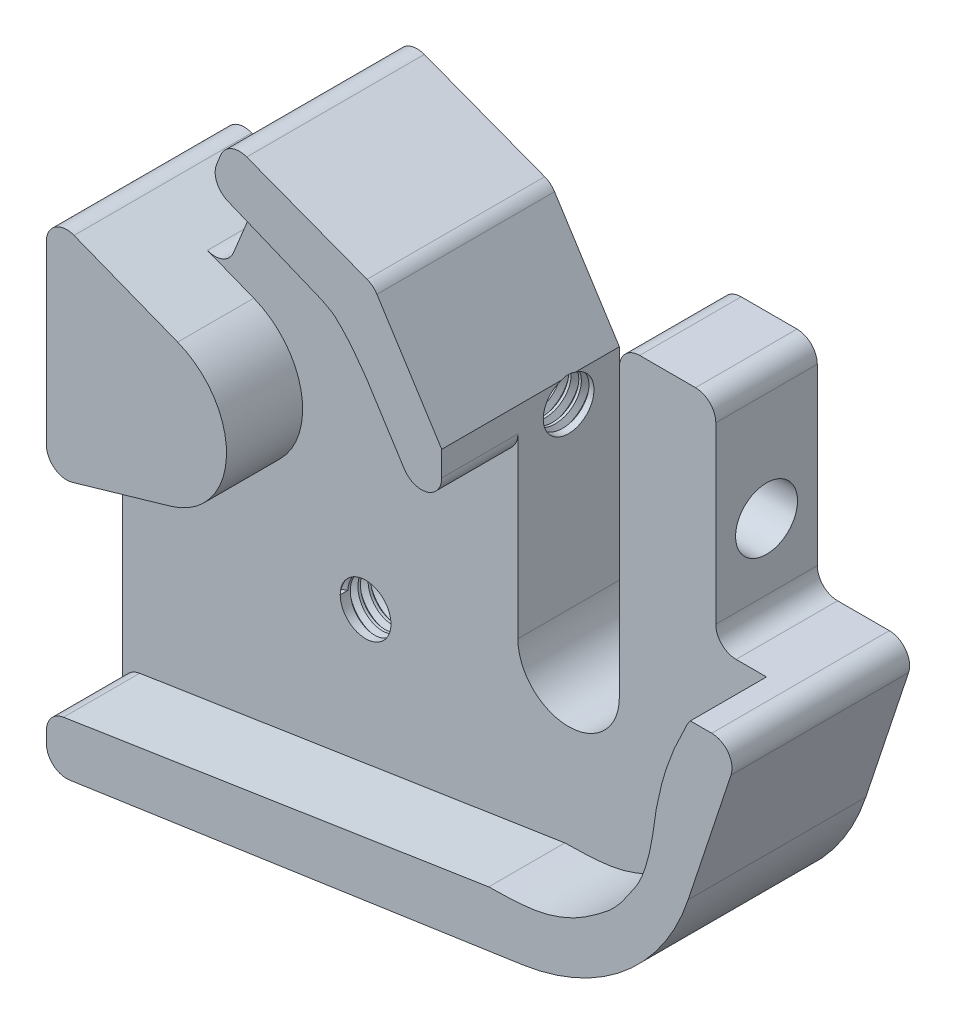
SolidWorks part; units mm, degrees
ref_plane "Front Plane" through (0, 0, 0) normal (0, 0, 1) x (1, 0, 0)
ref_plane "Top Plane" through (0, 0, 0) normal (0, 1, 0) x (1, 0, 0)
ref_plane "Right Plane" through (0, 0, 0) normal (1, 0, 0) x (0, 0, -1)
sketch "Sketch1" plane through (0, 0, 0) normal (0, 0, 1) x (1, 0, 0)
  line L0 (169.0465, 531.5792) -> (1384.9618, 942.3347) construction
  line L1 (17.1755, 0.269) -> (145.8355, -18.3486) construction
  line L2 (78.9683, 43.5936) -> (88.9683, 43.5936)
  line L3 (88.9683, 43.5936) -> (88.9683, 26.5936)
  line L4 (88.9683, 26.5936) -> (78.9683, 26.5936)
  line L5 (78.9683, 26.5936) -> (78.9683, 43.5936)
  line L6 (77.9414, 43.8024) -> (71.5407, 53.8656)
  line L7 (56.0381, 62.9033) -> (67.1668, 58.333)
  line L8 (88.9683, 43.5936) -> (88.9683, 61.7655)
  line L9 (88.9683, 61.7655) -> (98.4683, 61.7655)
  line L10 (77.9414, 43.8024) -> (78.9683, 42.1878)
  line L11 (20.6229, 24.1202) -> (53.1029, 33.5417)
  line L12 (23.9133, 59.0209) -> (55.1963, 46.7648)
  line L13 (56.0381, 62.9033) -> (50.2123, 48.7174)
  line L14 (70.5008, 62.7543) -> (72.231, 62.0968)
  line L15 (20.6228, 1.7639) -> (20.6229, 24.1202)
  line L16 (20.6229, 24.1202) -> (20.6229, 30.1202)
  line L17 (103.2745, 61.7655) -> (98.4683, 61.7655)
  line L18 (20.6229, 30.1202) -> (43.6301, 36.7939)
  line L19 (23.9133, 59.0209) -> (22.0894, 54.3655)
  line L20 (22.0894, 54.3655) -> (44.4958, 45.587)
  line L21 (78.9683, 43.5936) -> (78.9683, 49.4415)
  line L22 (57.9376, 67.5285) -> (70.5008, 62.7543)
  line L24 (40.0198, 35.7467) -> (40.0198, 47.3406)
  line L25 (40.0198, 47.3406) -> (40.0198, 52.7107)
  line L26 (56.0381, 62.9033) -> (57.9376, 67.5285)
  line L27 (103.4635, 40.5809) -> (108.336, 40.5809)
  line L28 (40.0198, 35.7467) -> (40.0198, 4.6135)
  line L29 (108.336, 40.5809) -> (99.307, 13.3233)
  line L30 (98.4683, 61.7655) -> (98.4683, 40.5809)
  line L31 (99.307, 13.3233) -> (20.6228, 1.7639)
  line L32 (83.9683, 43.5936) -> (83.9683, 46.6936)
  line L33 (20.6228, 6.4639) -> (20.6228, 6.7639)
  line L34 (20.6228, 6.7639) -> (83.6, 16.4882)
  line L35 (20.6229, 30.1202) -> (20.6229, 61.7655)
  line L36 (23.9133, 59.0209) -> (20.6229, 60.3101)
  line L37 (22.0894, 54.3655) -> (20.6229, 54.94)
  line L38 (73.7743, 50.3539) -> (77.9932, 53.0374) construction
  line L39 (77.9932, 53.0374) -> (71.1704, 63.7644)
  line L40 (77.9932, 53.0374) -> (78.9683, 51.5043)
  line L41 (78.9683, 51.5043) -> (78.9683, 49.4415)
  line L47 (98.4683, 40.5809) -> (103.4635, 40.5809)
  circle A0 centre (83.9683, 31.5936) radius 5
  circle A1 centre (83.9683, 38.5936) radius 5
  circle A5 centre (50.1903, 40.5872) radius 7.578
  circle A6 centre (103.2745, 54.3655) radius 4.4
  circle A7 centre (103.2745, 54.3655) radius 7.4
  circle A8 centre (83.9683, 31.5936) radius 20.3057
  spline S0 degree 3 poles (67.1668, 58.333) (67.5307, 58.1482) (68.2163, 57.8297) (69.7375, 56.3376) (70.7671, 54.998) (71.5407, 53.8656) knots 0 0 0 0 0.194176 0.353383 1 1 1 1
  spline S1 degree 3 poles (83.6, 16.4882) (85.4172, 16.5376) (87.878, 16.5192) (90.6726, 17.4205) (92.3949, 18.1773) (94.0998, 19.3373) (95.7619, 20.5842) (96.8381, 21.8934) (97.5722, 23.0215) (98.2993, 24.0127) (98.8168, 25.1807) (99.3382, 26.7948) (99.7545, 28.7331) (99.9792, 30.8782) (100.4112, 32.873) (100.8434, 34.6928) (101.4168, 36.2088) (101.8572, 37.4461) (102.3579, 38.4137) (102.8415, 39.4999) (103.165, 40.2018) (103.4635, 40.5809) knots 0 0 0 0 0.157684 0.206761 0.251698 0.319001 0.383658 0.429514 0.463788 0.499543 0.534878 0.573031 0.645405 0.704849 0.75836 0.820852 0.865423 0.897677 0.933689 0.958942 1 1 1 1
  spline S2 degree 3 poles (103.4635, 40.5809) (103.5281, 40.7021) (103.6539, 40.9177) (103.7777, 41.1891) (104.0324, 41.5752) (104.2845, 42.0418) (104.6133, 42.6639) (105.0506, 43.3284) (105.5376, 44.1633) (106.1189, 44.9679) (106.7473, 45.8247) (107.3304, 46.576) (107.8594, 47.2965) (108.3783, 47.8664) (108.8492, 48.4246) (109.2415, 48.9281) (109.5877, 49.4941) (110.1609, 50.7988) (110.3782, 52.0409) (110.5419, 52.9707) knots 0 0 0 0 0.032133 0.040138 0.080049 0.114202 0.15475 0.224504 0.279876 0.355143 0.430433 0.500504 0.552615 0.615873 0.660356 0.704255 0.748281 0.797656 1 1 1 1
  dimension "D7" = 5
  dimension "D5" = 8.8
  dimension "D6" = 14.8
  dimension "D1" = 130
  dimension "D2" = 10
  dimension "D3" = 17
  dimension "D4" = 9.5
  dimension "D8" = 5
  dimension "D9" = 5
  dimension "D10" = 5
extrude "Boss-Extrude1" add sketch "Sketch1" along normal blind 10 contours L34 S1 A8 L47 L30 L8 L3 L4 L5 L10 L6 | S0 L7 L13 L12 A5 L11 L28 L34 A8 L6 | A0 L5 L4 | A0 L4 L3 | A8 L30 A7 L9 L8 | A8 S1 L47 | L30 A7 region at (78.4335, 40.3907, 0) region at (93.3717, 55.5464, 0) region at (87.8514, 27.7104, 0) region at (80.0851, 27.7104, 0) region at (56.6282, 32.8832, 0) region at (97.4134, 54.3655, 0) region at (102.785, 40.1666, 0)
extrude "Boss-Extrude2" add sketch "Sketch1<3>" along normal blind 17.5 contours L7 S0 L6 A8 L41 L40 L39 L14 L22 L26 | L41 A8 L6 L10 L5 L21 | A5 | A5 L12 L25 L20 | A5 L20 L24 L18 | A5 L18 L28 L11 | A8 L34 L28 L31 | S1 L34 A8 | S1 A8 L29 L27 region at (77.4058, 47.7092, 0) region at (68.0812, 59.4299, 0) region at (58.9314, 9.8932, 0) region at (78.1518, 15.2189, 0) region at (105.2761, 36.6233, 0) region at (43.4702, 33.1986, 0) region at (43.8977, 48.9301, 0) region at (50.1903, 40.5872, 0) region at (41.5617, 41.668, 0)
sketch "Sketch1<3>" plane through (0, 0, 0) normal (0, 0, 1) x (1, 0, 0) same geometry as "Sketch1"
fillet "Fillet1" radius 2 13 edges at (108.336, 40.5809, 8.75) (98.4683, 61.7655, 5) (88.9683, 61.7655, 5) (57.9376, 67.5285, 8.75) (56.0381, 62.9033, 13.75) (78.9683, 42.1878, 13.75) (50.2123, 48.7174, 5) (98.4683, 40.5809, 5) (40.0198, 4.6135, 8.75) (40.0198, 9.759, 13.75) (40.0198, 29.7467, 13.75) (40.0198, 52.7107, 8.75) (72.231, 62.0968, 8.75)
sketch "Sketch4" plane through (88.9683, 0, 0) normal (-1, 0, 0) x (0, 0, 1)
  line L0 (5, 31.5936) -> (5, 49.0936)
  line L1 (10, 31.5936) -> (0, 31.5936) construction
  circle A0 centre (5, 49.0936) radius 3.05
  dimension "D1" = 17.5
extrude "Cut-Extrude2" cut sketch "Sketch4" against normal blind 30 contours A0 region at (88.9683, 46.9979, 7.0957)
hole_wizard "Tap Drill for M6x1.0 Tap3" positions "3DSketch7" profile "Sketch10" hole size "M6x1.0" standard "ANSI Metric"
sketch3d "3DSketch7"
  line L0 (98.4683, 49.0936, 5) -> (88.9683, 49.0936, 5) construction
  point P0 (88.9683, 49.0936, 5)
sketch "Sketch10" plane through (88.9683, 49.0936, 5) normal (0, 1, 0) x (0, 0, -1)
  line L0 (0, 0) -> (0, 31.5022)
  line L1 (0, 31.5022) -> (2.5, 30)
  line L2 (2.5, 30) -> (2.5, 0)
  line L5 (2.5, 0) -> (0, 0)
  line L10 (0, 31.5022) -> (-2.5, 30) construction
  line L11 (0, -6.35) -> (0, 107.95) construction
  dimension "Hole Dia." = 5
  dimension "Hole Depth" = 30
  dimension "Drill Angle" = 118
thread "Thread2" pitch 1 method cut profile "Thread Profile2" start angle 0, offset 0, length 20, pitch 1, diameter 5
ref_plane "Plane2" through (78.9683, 49.0936, 7.5) normal (0, -1, 0) x (0, 0, 1)
sketch "Thread Profile2" plane through (78.9683, 49.0936, 7.5) normal (0, -1, 0) x (0, 0, 1)
  line L0 (0, 0) -> (0, 1) construction
  line L1 (0, 0) -> (0.5413, 0.3125)
  line L2 (0.5413, 0.3125) -> (0.5413, 0.4375)
  line L3 (0.5413, 0.4375) -> (0, 0.75)
  line L4 (0.5413, 0.375) -> (0, 0.375) construction
  line L11 (0, 0) -> (0, 0.75)
  point P2 (0, 0)
  dimension "Pitch" = 1
  dimension "Profile_Angle" = 60
  dimension "Profile_Land" = 0.125
  dimension "Profile_Height" = 0.5413
sketch "Sketch14" plane through (0, 0, 10) normal (0, 0, 1) x (1, 0, 0)
  line L0 (83.9683, 26.5936) -> (63.9683, 26.5936)
  arc A0 (78.9683, 31.5936) -> (88.9683, 31.5936) centre (83.9683, 31.5936) ccw construction
hole_wizard "Tap Drill for M6x1.0 Tap4" positions "3DSketch11" profile "Sketch15" hole size "M6x1.0" standard "ANSI Metric"
sketch3d "3DSketch11"
  point P0 (63.9683, 26.5936, 10)
sketch "Sketch15" plane through (63.9683, 26.5936, 10) normal (1, 0, 0) x (0, -1, 0)
  line L0 (0, 0) -> (0, 31.5022)
  line L1 (0, 31.5022) -> (2.5, 30)
  line L2 (2.5, 30) -> (2.5, 0)
  line L5 (2.5, 0) -> (0, 0)
  line L10 (0, 31.5022) -> (-2.5, 30) construction
  line L11 (0, -6.35) -> (0, 107.95) construction
  dimension "Hole Dia." = 5
  dimension "Hole Depth" = 30
  dimension "Drill Angle" = 118
thread "Thread3" pitch 1 method cut profile "Thread Profile3" start angle 0, offset 0, length 20, pitch 1, diameter 5
ref_plane "Plane3" through (61.4683, 26.5936, 10) normal (0, -1, 0) x (-1, 0, 0)
sketch "Thread Profile3" plane through (61.4683, 26.5936, 10) normal (0, -1, 0) x (-1, 0, 0)
  line L0 (0, 0) -> (0, 1) construction
  line L1 (0, 0) -> (0.5413, 0.3125)
  line L2 (0.5413, 0.3125) -> (0.5413, 0.4375)
  line L3 (0.5413, 0.4375) -> (0, 0.75)
  line L4 (0.5413, 0.375) -> (0, 0.375) construction
  line L11 (0, 0) -> (0, 0.75)
  point P2 (0, 0)
  dimension "Pitch" = 1
  dimension "Profile_Angle" = 60
  dimension "Profile_Land" = 0.125
  dimension "Profile_Height" = 0.5413
